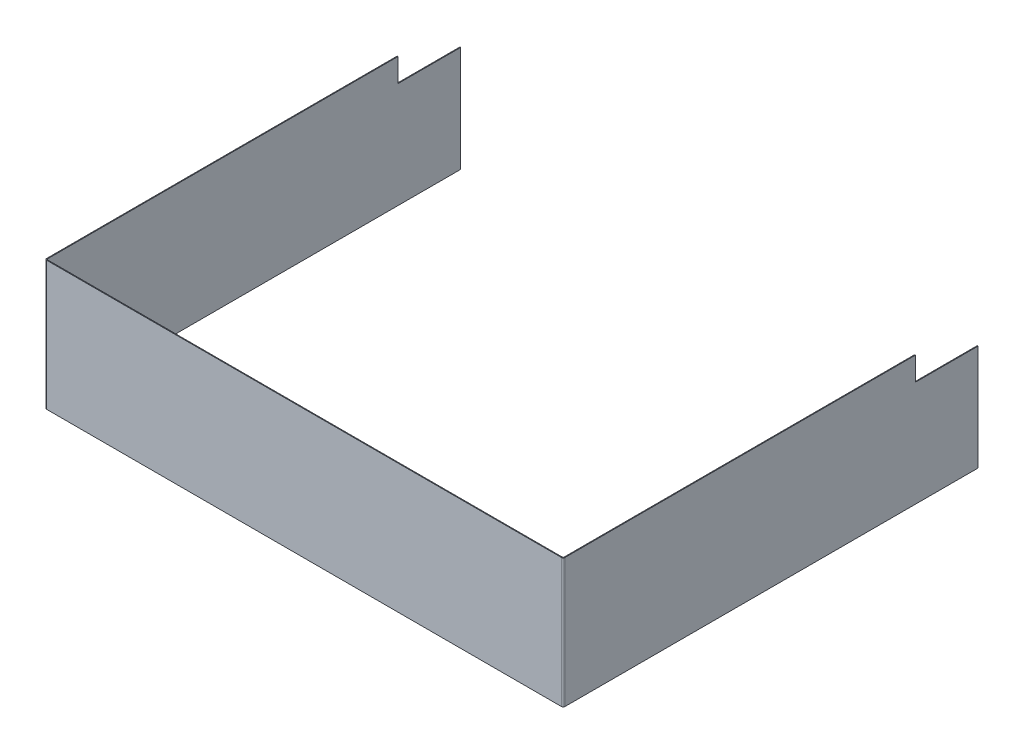
SolidWorks part; units mm, degrees
note: The reader was unsure of these and kept them because the rebuilt part matched: flange length of "Edge-Flange1".
ref_plane "Front Plane" through (0, 0, 0) normal (0, 0, 1) x (1, 0, 0)
ref_plane "Top Plane" through (0, 0, 0) normal (0, 1, 0) x (1, 0, 0)
ref_plane "Right Plane" through (0, 0, 0) normal (1, 0, 0) x (0, 0, -1)
sketch "Sketch1" plane through (0, 0, 0) normal (0, 0, 1) x (1, 0, 0)
  line L1 (330, -82.5) -> (-330, -82.5)
  line L2 (330, -82.5) -> (330, 82.5)
  line L3 (330, 82.5) -> (-330, 82.5)
  line L4 (-330, -82.5) -> (-330, 82.5)
  line L5 (330, -82.5) -> (-330, 82.5) construction
  line L6 (330, 82.5) -> (-330, -82.5) construction
  point P0 (0, 0)
  dimension "D1" = 660
  dimension "D2" = 165
base flange "Base-Flange1" sketch "Sketch1" thickness 1 reverse thickness direction no parameters "D1"=0.7366
edge flange "Edge-Flange1" sketch "Sketch10" flange profiles "Sketch10", "Sketch11" flange angle 90 flange length 530 flange position material outside bend radius 1 thickness 1 relief rectangular parameters "D6"=10, "D8"=1
sketch "Sketch10" plane through (330, 0, -1) normal (-1, 0, 0) x (0, 1, 0)
  line L2 (-82.5, 0) -> (-82.5, 529)
  line L3 (-82.5, 529) -> (82.5, 529)
  line L4 (82.5, 529) -> (82.5, 0)
  line L5 (82.5, 0) -> (-82.5, 0) construction
  line L6 (82.5, 0) -> (-82.5, 0)
sketch "Sketch11" plane through (-330, 0, -1) normal (1, 0, 0) x (0, -1, 0)
  line L0 (82.5, 0) -> (-82.5, 0) construction
  line L1 (82.5, 0) -> (-82.5, 0)
  line L2 (82.5, 0) -> (82.5, 529)
  line L3 (82.5, 529) -> (-82.5, 529)
  line L4 (-82.5, 529) -> (-82.5, 0)
bend "EdgeBend1" bend radius 1 bend angle 90 parameters "D5"=1
bend "EdgeBend2" bend radius 1 bend angle 90 parameters "D5"=2
sketch "Sketch12" plane through (331, 0, 0) normal (1, 0, 0) x (0, 0, -1)
  line L0 (530, 82.5) -> (530, -82.5) construction
  line L1 (530, 52.5) -> (450, 52.5)
  line L2 (530, 52.5) -> (530, 82.5)
  line L3 (530, 82.5) -> (450, 82.5)
  line L4 (450, 52.5) -> (450, 82.5)
  point P6 (530, 82.5)
  dimension "D1" = 30
  dimension "D2" = 80
extrude "Cut-Extrude1" cut sketch "Sketch12" against normal through all normal cut yes
sketch "Bend-Lines1" [suppressed] plane through (0, 0, 0) normal (0, 1, 0) x (1, 0, 0)
sketch "Bounding-Box1" [suppressed] plane through (0, 0, 0) normal (0, 1, 0) x (1, 0, 0)
sheet metal parameters "Sheet-Metal1" thickness 1 parameters "D1"=0.7366
flat pattern "Flat-Pattern1" [suppressed]
sketch "Bend-Lines2" plane through (0, 0, 0) normal (0, 1, 0) x (1, 0, 0)
sketch3d "Bounding-Box2" [suppressed]
  line L0 (310, -75, 0) -> (-310, -75, 0) construction
  line L1 (310, 75, 0) -> (-310, 75, 0) construction
  line L2 (310, -75, 0) -> (310, 75, 0) construction
  line L3 (-310, -75, 0) -> (-310, 75, 0) construction
sheet metal parameters "Sheet-Metal2" thickness 1 parameters "D1"=0.7366
flat pattern "Flat-Pattern1"
sketch "Bend-Lines2" plane through (0, 0, 0) normal (0, 0, 1) x (1, 0, 0)
  line L0 (-330.1781, 82.5) -> (-330.1781, -82.5) construction
  line L1 (330.1781, -82.5) -> (330.1781, 82.5) construction
  line L2 (-330.1781, 82.5) -> (-330.1781, -82.5) construction
  line L3 (330.1781, -82.5) -> (330.1781, 82.5) construction
sketch3d "Bounding-Box2" [suppressed]
  line L0 (-859.3562, -82.5, 0) -> (859.3562, -82.5, 0) construction
  line L1 (-859.3562, 82.5, 0) -> (859.3562, 82.5, 0) construction
  line L2 (-859.3562, -82.5, 0) -> (-859.3562, 82.5, 0) construction
  line L3 (859.3562, -82.5, 0) -> (859.3562, 82.5, 0) construction
bend of the flat pattern "EdgeBend1>1"
bend of the flat pattern "EdgeBend2>1"
sheet metal parameters "Sheet-Metal3" thickness 1 parameters "D1"=0.7366
flat pattern "Flat-Pattern1"
sketch "Bend-Lines2" plane through (0, 0, 0) normal (0, 0, 1) x (1, 0, 0)
  line L0 (-330.1781, 82.5) -> (-330.1781, -82.5) construction
  line L1 (330.1781, -82.5) -> (330.1781, 82.5) construction
  line L2 (-330.1781, 82.5) -> (-330.1781, -82.5) construction
  line L3 (330.1781, -82.5) -> (330.1781, 82.5) construction
sketch3d "Bounding-Box2" [suppressed]
  line L0 (-859.3562, -82.5, 0) -> (859.3562, -82.5, 0) construction
  line L1 (-859.3562, 82.5, 0) -> (859.3562, 82.5, 0) construction
  line L2 (-859.3562, -82.5, 0) -> (-859.3562, 82.5, 0) construction
  line L3 (859.3562, -82.5, 0) -> (859.3562, 82.5, 0) construction
bend of the flat pattern "EdgeBend1>1"
bend of the flat pattern "EdgeBend2>1"
